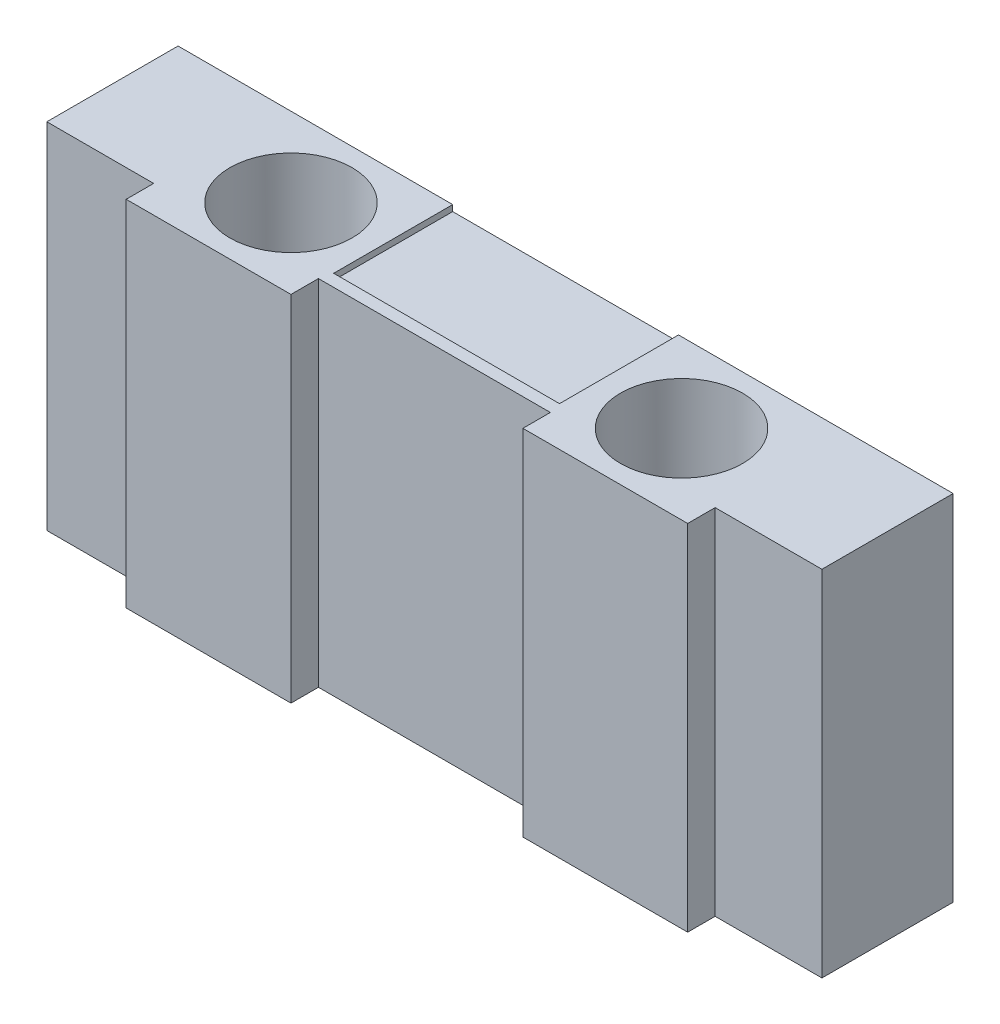
SolidWorks part; units mm, degrees
ref_plane "Alzado" through (0, 0, 0) normal (0, 0, 1) x (1, 0, 0)
ref_plane "Planta" through (0, 0, 0) normal (0, 1, 0) x (1, 0, 0)
ref_plane "Vista lateral" through (0, 0, 0) normal (1, 0, 0) x (0, 0, -1)
sketch "Croquis1" plane through (0, 0, 0) normal (0, 0, 1) x (1, 0, 0)
  line L0 (-1.85, 2.8) -> (1.85, 2.8)
  line L1 (6.35, 2.9) -> (1.85, 2.9)
  line L2 (6.35, 2.9) -> (6.35, -2.9)
  line L3 (6.35, -2.9) -> (1.85, -2.9)
  line L4 (-6.35, 2.9) -> (-6.35, -2.9)
  line L5 (6.35, 2.9) -> (-6.35, -2.9) construction
  line L6 (6.35, -2.9) -> (-6.35, 2.9) construction
  line L7 (-1.85, 2.9) -> (-6.35, 2.9)
  line L8 (1.85, -2.9) -> (1.85, -2.8)
  line L10 (-1.85, -2.9) -> (-1.85, -2.8)
  line L11 (1.85, -2.9) -> (-1.85, 2.9) construction
  line L12 (1.85, 2.9) -> (-1.85, -2.9) construction
  line L13 (-1.85, -2.8) -> (1.85, -2.8)
  line L14 (-1.85, 2.8) -> (-1.85, 2.9)
  line L15 (1.85, 2.8) -> (1.85, 2.9)
  line L16 (-1.85, -2.9) -> (-6.35, -2.9)
  point P0 (0, 0)
  point P7 (0, 0)
  dimension "D1" = 0.1
  dimension "D2" = 0.1
extrude "Saliente-Extruir1" add sketch "Croquis1" along normal blind 2.6
sketch "Croquis2" plane through (0, 0, 0) normal (0, 1, 0) x (1, 0, 0)
  line L4 (-6.35, -2.6) -> (-6.35, 0) construction
  line L5 (-6.35, -2.6) -> (-6.35, 0) construction
  line L6 (6.35, -2.6) -> (6.35, 0) construction
  line L7 (6.35, -2.6) -> (6.35, 0) construction
  line L9 (-6.35, -1.3) -> (6.35, -1.3) construction
  line L11 (3.2, -0.5917) -> (-3.2, -0.5917) construction
  circle A0 centre (-3.2, -1.3) radius 1
  circle A1 centre (3.2, -1.3) radius 1
  point P0 (0, -1.3)
  dimension "D1" = 2
extrude "Cortar-Extruir1" cut sketch "Croquis2" against normal mid plane 6
sketch "Croquis4" plane through (0, 0, 2.6) normal (0, 0, 1) x (1, 0, 0)
  line L1 (-1.85, 2.8) -> (1.85, 2.8)
  line L2 (-1.85, 2.8) -> (-1.85, 2.9)
  line L3 (-1.85, 2.9) -> (1.85, 2.9)
  line L4 (1.85, 2.8) -> (1.85, 2.9)
  line L5 (-1.85, -2.9) -> (1.85, -2.9)
  line L6 (-1.85, -2.9) -> (-1.85, -2.8)
  line L7 (-1.85, -2.8) -> (1.85, -2.8)
  line L8 (1.85, -2.9) -> (1.85, -2.8)
extrude "Saliente-Extruir2" add sketch "Croquis4" against normal blind 0.8
chamfer "Chaflán1" distance 0.15 angle 45 2 edges at (0, -2.9, 1.8) (0, 2.9, 1.8)
sketch "Croquis5" plane through (0, 0, 2.6) normal (0, 0, 1) x (1, 0, 0)
  line L0 (6.35, 2.9) -> (-6.35, 2.9) construction
  line L1 (1.9, -2.9) -> (-1.9, -2.9)
  line L2 (1.9, -2.9) -> (1.9, 2.9)
  line L3 (1.9, 2.9) -> (-1.9, 2.9)
  line L4 (-1.9, -2.9) -> (-1.9, 2.9)
  line L5 (1.9, -2.9) -> (-1.9, 2.9) construction
  line L6 (1.9, 2.9) -> (-1.9, -2.9) construction
  line L7 (-1.9, 2.9) -> (-4.6, 2.9) construction
  line L8 (1.9, 2.9) -> (4.6, 2.9) construction
  line L9 (-4.6, 2.9) -> (-6.35, 2.9)
  line L10 (-4.6, 2.9) -> (-4.6, -2.9)
  line L11 (-4.6, -2.9) -> (-6.35, -2.9)
  line L12 (-6.35, 2.9) -> (-6.35, -2.9)
  line L14 (4.6, 2.9) -> (6.35, 2.9)
  line L15 (4.6, 2.9) -> (4.6, -2.9)
  line L16 (4.6, -2.9) -> (6.35, -2.9)
  line L17 (6.35, 2.9) -> (6.35, -2.9)
  point P0 (0, 0)
  dimension "D1" = 3.8
  dimension "D2" = 2.7
  dimension "D3" = 2.7
extrude "Cortar-Extruir2" cut sketch "Croquis5" against normal blind 0.45
